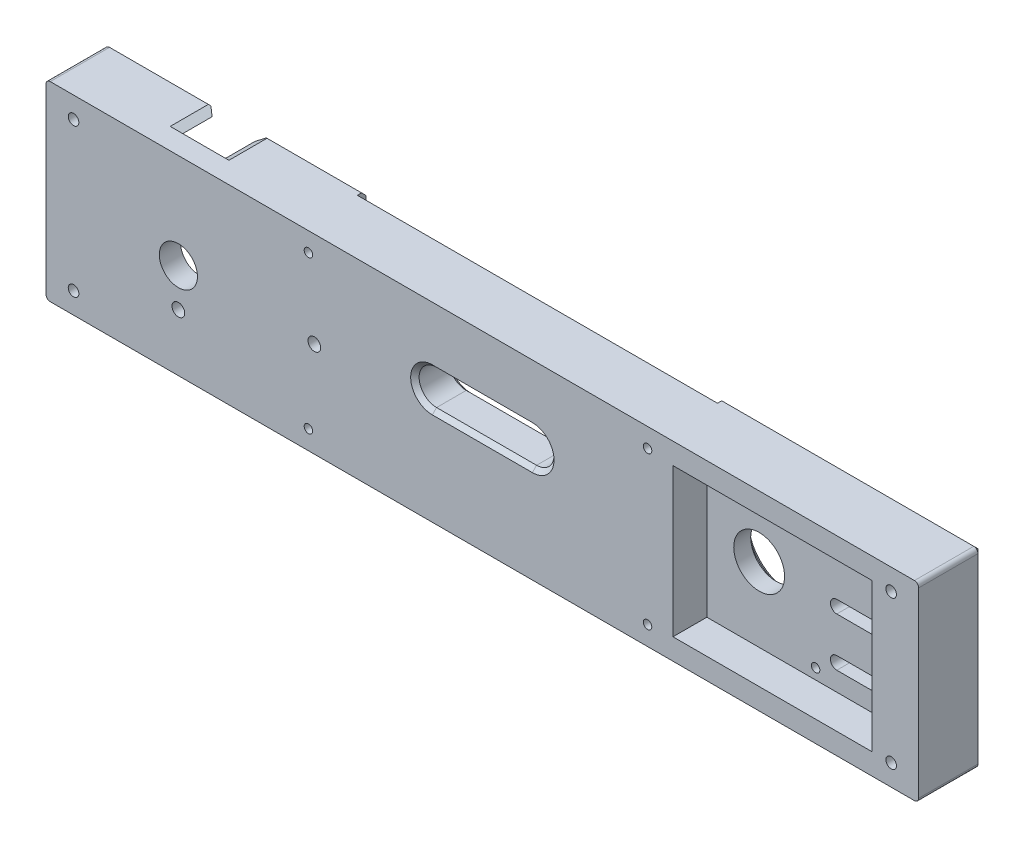
SolidWorks part; units mm, degrees
ref_plane "Front" through (0, 0, 0) normal (0, 0, 1) x (1, 0, 0)
ref_plane "Top" through (0, 0, 0) normal (0, 1, 0) x (1, 0, 0)
ref_plane "Right" through (0, 0, 0) normal (1, 0, 0) x (0, 0, -1)
sketch "草图1" plane through (0, 0, 0) normal (0, 0, 1) x (1, 0, 0)
  line L0 (0, 45) -> (206, 0) construction
  line L1 (0, 0) -> (206, 0)
  line L2 (0, 0) -> (0, 45)
  line L3 (0, 45) -> (206, 45)
  line L4 (206, 0) -> (206, 45)
  line L5 (206, 45) -> (0, 0) construction
  line L7 (60.5, 0) -> (145.5, 0)
  line L8 (60.5, 0) -> (60.5, 45)
  line L9 (60.5, 45) -> (145.5, 45)
  line L10 (145.5, 0) -> (145.5, 45)
  line L11 (60.5, 0) -> (145.5, 45) construction
  line L12 (60.5, 45) -> (145.5, 0) construction
  line L13 (66, 1) -> (140, 1)
  line L14 (66, 1) -> (66, 44)
  line L15 (66, 44) -> (140, 44)
  line L16 (140, 1) -> (140, 44)
  line L17 (66, 1) -> (140, 44) construction
  line L18 (66, 44) -> (140, 1) construction
  circle A0 centre (63.3502, 22.5) radius 1.5
  point P5 (103, 22.5)
  point P17 (103, 22.5)
  dimension "D5" = 3
  dimension "D1" = 206
  dimension "D2" = 45
  dimension "D3" = 85
  dimension "D4" = 45
  dimension "D6" = 74
  dimension "D7" = 43
extrude "凸台-拉伸1" add sketch "草图1" along normal blind 15 contours L1 L4 L3 L2
extrude "切除-拉伸1" cut sketch "草图1<4>" along normal blind 2 contours L8 L9 L10 L7
sketch "草图1<4>" plane through (0, 0, 0) normal (0, 0, 1) x (1, 0, 0) same geometry as "草图1"
extrude "切除-拉伸2" cut sketch "草图1<5>" along normal blind 71 contours L16 L15 L14 L13 | A0
sketch "草图1<5>" plane through (0, 0, 0) normal (0, 0, 1) x (1, 0, 0) same geometry as "草图1"
sketch "草图2" plane through (0, 0, 0) normal (0, 0, -1) x (-1, 0, 0)
  line L0 (-31.25, 22.5) -> (-31.25, 44.5)
  line L3 (-31.25, 45) -> (-31.25, 0) construction
  circle A0 centre (-31.25, 22.5) radius 22
  circle A1 centre (-31.25, 22.5) radius 4.5
  dimension "D1" = 44
  dimension "D3" = 9
extrude "切除-拉伸4" cut sketch "草图2" against normal blind 10 contours A0 L0 | L0 A0 region at (16.1337, 37.6163, 0)
extrude "切除-拉伸5" cut sketch "草图2<3>" against normal blind 50 contours A1 L0 | L0 A1 region at (28.158, 25.592, 0)
sketch "草图2<3>" plane through (0, 0, 0) normal (0, 0, -1) x (-1, 0, 0) same geometry as "草图2"
sketch "草图3" plane through (0, 0, 0) normal (0, 0, -1) x (-1, 0, 0)
  line L0 (-140, 44) -> (-66, 1) construction
  line L1 (-203, 2) -> (-3, 2)
  line L2 (-203, 2) -> (-203, 43)
  line L3 (-203, 43) -> (-3, 43)
  line L4 (-3, 2) -> (-3, 43)
  line L5 (-203, 2) -> (-3, 43) construction
  line L6 (-203, 43) -> (-3, 2) construction
  line L7 (-140, 1) -> (-66, 44) construction
  line L8 (-15.5, 43) -> (-15.5, 2)
  point P0 (-103, 22.5)
  point P15 (-3, 22.5)
  dimension "D1" = 200
  dimension "D2" = 41
  dimension "D3" = 12.5
sketch "草图4" plane through (0, 0, 15) normal (0, 0, 1) x (1, 0, 0)
  line L0 (31.25, 13.5) -> (31.25, 22.5)
  line L1 (31.25, 22.5) -> (31.25, 13.5)
  circle A0 centre (31.25, 22.5) radius 9
  circle A1 centre (31.25, 13.5) radius 1.5
  dimension "D1" = 18
  dimension "D3" = 3
  dimension "D2" = 0
extrude "切除-拉伸6" cut sketch "草图4" against normal blind 44 and the other way blind 17 contours A1
sketch "草图5" plane through (0, 0, 0) normal (0, 0, -1) x (-1, 0, 0)
  line L0 (-186.6654, 34) -> (-178.6654, 34) construction
  line L1 (-186.6654, 35.5) -> (-178.6654, 35.5)
  line L2 (-186.6654, 32.5) -> (-178.6654, 32.5)
  line L3 (-186.6654, 11) -> (-178.6654, 11) construction
  line L4 (-186.6654, 12.5) -> (-178.6654, 12.5)
  line L5 (-186.6654, 9.5) -> (-178.6654, 9.5)
  line L6 (-182.6654, 45) -> (-182.6654, 0) construction
  line L7 (-145.5, 45) -> (-206, 45) construction
  line L8 (-145.5, 0) -> (-206, 0) construction
  line L9 (-186.6654, 22.5) -> (-178.6654, 22.5) construction
  line L10 (-186.6654, 24) -> (-178.6654, 24)
  line L11 (-186.6654, 21) -> (-178.6654, 21)
  arc A0 (-186.6654, 35.5) -> (-186.6654, 32.5) centre (-186.6654, 34) ccw
  arc A1 (-178.6654, 32.5) -> (-178.6654, 35.5) centre (-178.6654, 34) ccw
  arc A2 (-186.6654, 12.5) -> (-186.6654, 9.5) centre (-186.6654, 11) ccw
  arc A3 (-178.6654, 9.5) -> (-178.6654, 12.5) centre (-178.6654, 11) ccw
  arc A4 (-186.6654, 24) -> (-186.6654, 21) centre (-186.6654, 22.5) ccw
  arc A5 (-178.6654, 21) -> (-178.6654, 24) centre (-178.6654, 22.5) ccw
  point P2 (-182.6654, 34)
  point P9 (-182.6654, 11)
  point P14 (-182.6654, 34)
  point P15 (-182.6654, 11)
  point P22 (-182.6654, 22.5)
  point P27 (-182.6654, 22.5)
  point P32 (-189.0753, 23.5128)
  dimension "D2" = 1.5
  dimension "D8" = 1.5
  dimension "D9" = 1.5
  dimension "D1" = 8
  dimension "D3" = 8
  dimension "D4" = 11.5
  dimension "D5" = 45
  dimension "D6" = 11.5
  dimension "D7" = 8
extrude "切除-拉伸7" cut sketch "草图5" against normal blind 14
chamfer "倒角1" distance 1 angle 45 12 edges at (177.1654, 34, 0) (182.6654, 35.5, 0) (188.1654, 34, 0) (182.6654, 32.5, 0) (188.1654, 11, 0) (182.6654, 9.5, 0) (182.6654, 12.5, 0) (177.1654, 11, 0) (188.1654, 22.5, 0) (182.6654, 21, 0) (182.6654, 24, 0) (177.1654, 22.5, 0)
chamfer "倒角2" distance 2 angle 45 1 edges at (9.25, 22.5, 0)
sketch "草图6" plane through (0, 0, 0) normal (0, 0, -1) x (-1, 0, 0)
  line L0 (-31.25, 23) -> (-31.25, -16.3208)
  line L1 (-31.25, -16.3208) -> (-31.25, 54.112)
  line L2 (-31.25, 41) -> (-53.9606, 54.112)
  line L3 (-53.9606, 54.112) -> (-8.5394, 54.112)
  line L4 (-8.5394, 54.112) -> (-31.25, 41)
  line L5 (-31.25, 5) -> (-68.1787, -16.3208)
  line L6 (-68.1787, -16.3208) -> (5.6787, -16.3208)
  line L7 (5.6787, -16.3208) -> (-31.25, 5)
  point P3 (-31.25, 5)
  point P5 (-31.25, 41)
  line M5 (0, 45) -> (-22.8984, 45)
  arc M6 (-22.8984, 45) -> (-22.8984, 0) centre (-31.25, 22.5) cw
  line M7 (-22.8984, 0) -> (0, 0)
  dimension "D1" = 18
  dimension "D2" = 18
  dimension "D3" = 60
  dimension "D4" = 60
  dimension "D5" = 60
  dimension "D6" = 60
extrude "切除-拉伸9" cut sketch "草图6" against normal up to surface (10 mm away) contours L6 L7 L1 M7 M6 | L5 L6 L1 | L4 L3 L1 M6 M5 | L3 L2 L1 region at (18.9403, -9.2141, 0) region at (43.5596, -9.2139, 0) region at (38.8202, 49.7413, 0) region at (23.6798, 49.7413, 0) up to face at (29.75, 13.5, 10)
sketch "草图7" plane through (0, 0, 0) normal (0, 0, -1) x (-1, 0, 0)
  line L0 (-145.5, 22.5) -> (-203, 22.5) construction
  line L3 (-145.5, 0) -> (-145.5, 45) construction
  line L4 (-203, 2) -> (-203, 43) construction
  circle A0 centre (-160.3418, 22.5) radius 6
  circle A1 centre (-160.3418, 22.5) radius 8.5
  dimension "D3" = 12
  dimension "D4" = 17
extrude "切除-拉伸10" cut sketch "草图7" against normal blind 182 contours A0 | L0 A0 region at (160.3418, 19.9535, 0) region at (160.3418, 25.0465, 0)
extrude "切除-拉伸11" cut sketch "草图7<4>" against normal blind 3 contours A1 A0 | L0 A1 A0 region at (160.3418, 14.1901, 0) region at (153.0918, 22.6901, 0)
sketch "草图7<4>" plane through (0, 0, 0) normal (0, 0, -1) x (-1, 0, 0) same geometry as "草图7"
chamfer "倒角3" distance 1 angle 45 1 edges at (151.8418, 22.5, 0)
sketch "草图9" plane through (0, 0, 0) normal (0, 0, -1) x (-1, 0, 0)
  line L0 (-206, 0) -> (-206, 45) construction
  line L1 (-6.5, 5) -> (-199.5, 5)
  line L2 (-6.5, 5) -> (-6.5, 40)
  line L3 (-6.5, 40) -> (-199.5, 40)
  line L4 (-199.5, 5) -> (-199.5, 40)
  line L5 (-6.5, 5) -> (-199.5, 40) construction
  line L6 (-6.5, 40) -> (-199.5, 5) construction
  line L7 (-145.5, 0) -> (-206, 0) construction
  circle A0 centre (-199.5, 40) radius 1.25
  circle A1 centre (-199.5, 40) radius 2.5
  circle A2 centre (-199.5, 5) radius 1.25
  circle A3 centre (-199.5, 5) radius 2.5
  circle A4 centre (-6.5, 5) radius 1.25
  circle A5 centre (-6.5, 5) radius 2.5
  circle A6 centre (-6.5, 40) radius 1.25
  circle A7 centre (-6.5, 40) radius 2.5
  point P0 (-103, 22.5)
  dimension "D3" = 2.5
  dimension "D4" = 5
  dimension "D1" = 6.5
  dimension "D2" = 5
extrude "切除-拉伸12" cut sketch "草图9" against normal blind 182 contours A6 | A4 | A2 | A0
extrude "切除-拉伸13" cut sketch "草图9<3>" against normal blind 3 contours A1 | A3 | A5 | A7
sketch "草图9<3>" plane through (0, 0, 0) normal (0, 0, -1) x (-1, 0, 0) same geometry as "草图9"
fillet "圆角1" radius 1 4 edges at (206, 0, 7.5) (206, 45, 7.5) (0, 0, 7.5) (0, 45, 7.5)
sketch "草图10" plane through (0, 0, 15) normal (0, 0, 1) x (1, 0, 0)
  line L0 (203, 43) -> (3, 43) construction
  line L1 (148, 40) -> (195, 40)
  line L2 (148, 40) -> (148, 5)
  line L3 (148, 5) -> (195, 5)
  line L4 (195, 40) -> (195, 5)
  line L5 (203, 2) -> (3, 2) construction
  line L6 (203, 2) -> (203, 43) construction
  line L7 (140, 1) -> (140, 44) construction
  dimension "D1" = 3
  dimension "D2" = 3
  dimension "D3" = 8
  dimension "D4" = 8
extrude "切除-拉伸14" cut sketch "草图10" against normal blind 8
sketch "草图11" plane through (0, 0, 7) normal (0, 0, 1) x (1, 0, 0)
  line L1 (170.77, 40) -> (170.77, 5)
  line L2 (186.6654, 21) -> (178.6654, 21) construction
  line L3 (195, 40) -> (148, 40) construction
  line L4 (182.6654, 40) -> (182.6654, 5)
  line L8 (148, 5) -> (195, 5) construction
  line L9 (182.6654, 21) -> (182.6654, 24)
  line L10 (178.6654, 24) -> (186.6654, 24) construction
  line L11 (173.6654, 7.5) -> (191.6654, 7.5)
  line L12 (173.6654, 7.5) -> (173.6654, 37.5)
  line L13 (173.6654, 37.5) -> (191.6654, 37.5)
  line L14 (191.6654, 7.5) -> (191.6654, 37.5)
  line L15 (173.6654, 7.5) -> (191.6654, 37.5) construction
  line L16 (173.6654, 37.5) -> (191.6654, 7.5) construction
  line L17 (195, 5) -> (195, 40) construction
  circle A0 centre (191.6654, 37.5) radius 1
  circle A1 centre (173.6654, 37.5) radius 1
  circle A2 centre (173.6654, 7.5) radius 1
  circle A3 centre (191.6654, 7.5) radius 1
  point P9 (182.6654, 22.5)
  point P15 (182.6654, 22.5)
  point P26 (170.77, 22.5)
  dimension "D7" = 24.23
  dimension "D8" = 2.5
  dimension "D9" = 2.5
  dimension "D10" = 2.8954
  dimension "D3" = 2
  dimension "D4" = 2
  dimension "D5" = 2
  dimension "D6" = 2
  dimension "D1" = 18
  dimension "D2" = 30
  dimension "D11" = 3.3346
extrude "切除-拉伸15" cut sketch "草图11" against normal blind 3 contours A1 | A2 | A3 | A0
chamfer "倒角4" distance 1 angle 45 12 edges at (175.25, 0, 0) (205.7071, 0.2929, 0) (206, 22.5, 0) (205.7071, 44.7071, 0) (175.25, 45, 0) (50.2051, 0, 0) (50.0508, 45, 0) (11.9492, 0, 0) (11.9492, 45, 0) (0.2929, 0.2929, 0) (0.2929, 44.7071, 0) (0, 22.5, 0)
sketch "草图12" plane through (0, 0, 15) normal (0, 0, 1) x (1, 0, 0)
  line L1 (64.9661, 4.5) -> (142, 4.5)
  line L2 (64.9661, 4.5) -> (64.9661, 40.5)
  line L3 (64.9661, 40.5) -> (142, 40.5)
  line L4 (142, 4.5) -> (142, 40.5)
  line L5 (64.9661, 4.5) -> (142, 40.5) construction
  line L6 (64.9661, 40.5) -> (142, 4.5) construction
  line L7 (64.9661, 40.5) -> (61.95, 40.5)
  line L8 (64.9661, 40.5) -> (64.9661, 4.5)
  line L9 (64.9661, 4.5) -> (61.95, 4.5)
  line L11 (140, 1) -> (140, 44) construction
  line L12 (148, 40) -> (148, 5) construction
  line L13 (1, 45) -> (205, 45) construction
  line L14 (1, 0) -> (205, 0) construction
  circle A0 centre (61.95, 40.5) radius 1
  circle A1 centre (61.95, 4.5) radius 1
  circle A2 centre (142, 4.5) radius 1
  circle A3 centre (142, 40.5) radius 1
  point P0 (103.4831, 22.5)
  dimension "D1" = 2
  dimension "D2" = 2
  dimension "D3" = 2
  dimension "D4" = 2
  dimension "D6" = 2
  dimension "D7" = 6
  dimension "D8" = 4.5
  dimension "D9" = 4.5
  dimension "D11" = 36
extrude "切除-拉伸16" cut sketch "草图12" against normal blind 5 contours A0 | A1 | A2 | A3
sketch "草图13" plane through (0, 0, 2) normal (0, 0, -1) x (-1, 0, 0)
  line L0 (-140, 44) -> (-66, 1)
  line L2 (-141.3812, 3.3187) -> (-64.6187, 3.3187)
  line L3 (-141.3812, 3.3187) -> (-141.3812, 41.6813)
  line L4 (-141.3812, 41.6813) -> (-64.6187, 41.6813)
  line L5 (-64.6187, 3.3187) -> (-64.6187, 41.6813)
  line L6 (-141.3812, 3.3187) -> (-64.6187, 41.6813) construction
  line L7 (-141.3812, 41.6813) -> (-64.6187, 3.3187) construction
  line L8 (-139.5, 1.05) -> (-66.5, 1.05)
  line L9 (-139.5, 1.05) -> (-139.5, 43.95)
  line L10 (-139.5, 43.95) -> (-66.5, 43.95)
  line L11 (-66.5, 1.05) -> (-66.5, 43.95)
  line L12 (-139.5, 1.05) -> (-66.5, 43.95) construction
  line L13 (-139.5, 43.95) -> (-66.5, 1.05) construction
  line L14 (-72.295, 7.155) -> (-133.705, 7.155)
  line L15 (-72.295, 7.155) -> (-72.295, 37.845)
  line L16 (-72.295, 37.845) -> (-133.705, 37.845)
  line L17 (-133.705, 7.155) -> (-133.705, 37.845)
  line L18 (-72.295, 7.155) -> (-133.705, 37.845) construction
  line L19 (-72.295, 37.845) -> (-133.705, 7.155) construction
  point P4 (-103, 22.5)
  point P9 (-103, 22.5)
  point P14 (-103, 22.5)
  dimension "D1" = 3.8363
  dimension "D2" = 7.6762
  dimension "D3" = 42.9
  dimension "D4" = 73
  dimension "D5" = 30.69
  dimension "D6" = 61.41
sketch "草图15" plane through (0, 0, 15) normal (0, 0, 1) x (1, 0, 0)
  line L0 (66, 44) -> (140, 44) construction
  line L1 (140, 1) -> (140, 44) construction
  line L2 (66, 1) -> (140, 1) construction
  line L3 (66, 1) -> (66, 44) construction
  line L4 (66, 44) -> (140, 44)
  line L5 (140, 1) -> (140, 44)
  line L6 (66, 1) -> (140, 1)
  line L7 (66, 1) -> (66, 44)
  line L8 (91.1969, 27.0832) -> (114.8031, 27.0832) construction
  line L9 (91.1969, 31.2027) -> (114.8031, 31.2027)
  line L10 (91.1969, 22.9636) -> (114.8031, 22.9636)
  arc A0 (91.1969, 31.2027) -> (91.1969, 22.9636) centre (91.1969, 27.0832) ccw
  arc A1 (114.8031, 22.9636) -> (114.8031, 31.2027) centre (114.8031, 27.0832) ccw
  point P6 (103, 27.0832)
extrude "凸台-拉伸2" add sketch "草图15" against normal blind 9
chamfer "倒角5" distance 1 angle 45 8 edges at (103, 22.9636, 15) (118.9226, 27.0832, 15) (87.0774, 27.0832, 15) (103, 31.2027, 15) (103, 22.9636, 6) (118.9226, 27.0832, 6) (87.0774, 27.0832, 6) (103, 31.2027, 6)
